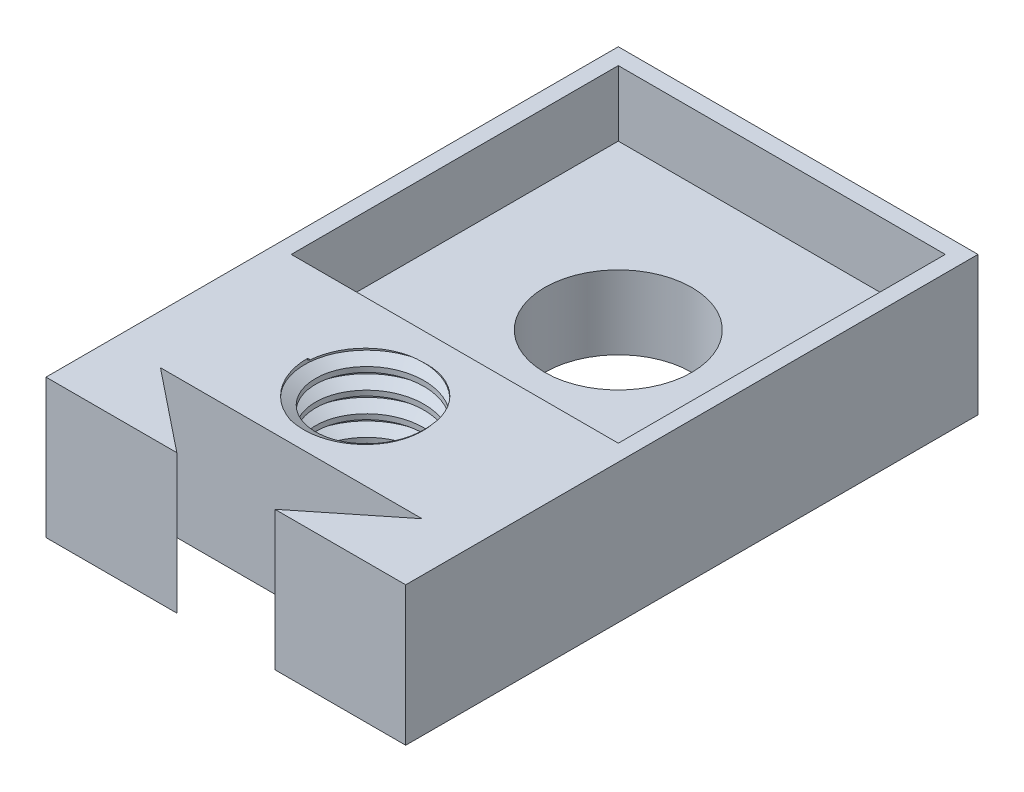
SolidWorks part; units mm, degrees
ref_plane "Front Plane" through (0, 0, 0) normal (0, 0, 1) x (1, 0, 0)
ref_plane "Top Plane" through (0, 0, 0) normal (0, 1, 0) x (1, 0, 0)
ref_plane "Right Plane" through (0, 0, 0) normal (1, 0, 0) x (0, 0, -1)
sketch "Sketch1" plane through (0, 0, 0) normal (0, 1, 0) x (1, 0, 0)
  line L1 (-10, -10) -> (10, -10)
  line L2 (-10, -10) -> (-10, 10)
  line L3 (-10, 10) -> (10, 10)
  line L4 (10, -10) -> (10, 10)
  line L5 (-10, -10) -> (10, 10) construction
  line L6 (-10, 10) -> (10, -10) construction
  line L7 (-11, -11) -> (11, -11)
  line L8 (-11, -11) -> (-11, 11)
  line L9 (-11, 11) -> (11, 11)
  line L10 (11, -11) -> (11, 11)
  line L11 (-11, -11) -> (11, 11) construction
  line L12 (-11, 11) -> (11, -11) construction
  point P0 (0, 0)
  point P6 (0, 0)
  dimension "D1" = 20
  dimension "D2" = 20
  dimension "D3" = 22
  dimension "D4" = 22
extrude "Boss-Extrude1" add sketch "Sketch1" along normal blind 5 and the other way blind 3.5
extrude "Boss-Extrude2" add sketch "Sketch1<2>" along normal blind 1 and the other way blind 3.5 contours L1 L4 L3 L2
sketch "Sketch1<2>" plane through (0, 0, 0) normal (0, 1, 0) x (1, 0, 0) same geometry as "Sketch1"
sketch "Sketch2" plane through (0, -3.5, 0) normal (0, -1, 0) x (1, 0, 0)
  circle A0 centre (0, 0) radius 4.5
  circle A1 centre (0, 0) radius 7
  dimension "D1" = 9
extrude "Cut-Extrude1" cut sketch "Sketch2" against normal blind 7 contours A0
sketch "Sketch3" plane through (0, 0, 0) normal (0, 1, 0) x (1, 0, 0)
  line L0 (0, -11) -> (0, -24)
  line L1 (-11, -11) -> (11, -11)
  line L2 (-11, -11) -> (-11, -24)
  line L3 (-11, -24) -> (11, -24)
  line L4 (11, -11) -> (11, -24)
  line L5 (-10.75, -24) -> (0, -24)
  line L6 (-8, -20) -> (-8, -24)
  line L7 (-10.75, -24) -> (-9.9027, -24)
  line L8 (-8, -20) -> (8, -20)
  line L9 (-8, -24) -> (8, -24)
  line L10 (-10.75, -24) -> (-13.75, -24)
  line L11 (0, -24) -> (-2.0006, -24)
  line L12 (0, -24) -> (-1, -24)
  line L13 (-11, 11) -> (-11, -11) construction
  line L14 (-1, -24) -> (-1, -21.75)
  line L15 (0, -24) -> (-3, -24)
  line L16 (10.75, -24) -> (13.75, -24)
  line L17 (8, -20) -> (8, -24)
  line L18 (-8, -20) -> (8, -24) construction
  line L19 (-8, -24) -> (8, -20) construction
  line L20 (-11, -9) -> (-11, -11)
  line L21 (11, -9) -> (11, -11)
  line L22 (10.75, -24) -> (0, -24)
  line L23 (-8, -20) -> (-3, -24)
  line L24 (1, -24) -> (1, -21.75)
  line L25 (8, -20) -> (3, -24)
  spline S0 degree 1 poles (-8, -20) (-1, -21.75) knots 0 0 1 1
  spline S1 degree 1 poles (8, -20) (1, -21.75) knots 0 0 1 1
  point P9 (0, -22)
  dimension "D1" = 10.75
  dimension "D3" = 13
  dimension "D4" = 3
  dimension "D5" = 4
  dimension "D9" = 0
extrude "Boss-Extrude4" add sketch "Sketch3" along normal blind 5 and the other way blind 3.5 contours L2 L20 L10 | L6 L8 L0 L1 L2 L3 L5 | L8 L17 L3 L4 L1 L0 | L23 L6 L5 | L17 L25 L3 region at (5.9324, 0, 16.2027) region at (-5.9324, 0, 16.2027) region at (-6.3333, 0, 22.6667) region at (6.3333, 0, 22.6667)
sketch "Sketch4" plane through (0, 5, 0) normal (0, 1, 0) x (1, 0, 0)
  line L2 (0, -4.675) -> (0, 4.675) construction
  line L4 (3, -24) -> (11, -24) construction
  circle A0 centre (0, -15) radius 4
  dimension "D2" = 8
  dimension "D1" = 9
extrude "Cut-Extrude2" cut sketch "Sketch4" against normal blind 10
thread "Thread1" pitch 1.25 method extrude trim with start face yes trim with end face yes profile "Thread Profile2" start angle 0, offset 1, length 10, pitch 1.25, diameter 8
ref_plane "Plane2" through (-4, 6, 15) normal (0, 0, 1) x (-1, 0, 0)
sketch "Thread Profile2" plane through (-4, 6, 15) normal (0, 0, 1) x (-1, 0, 0)
  line L0 (0, 0) -> (0, 1.25) construction
  line L11 (0, 0) -> (0, 1.0937)
  line L12 (0, 1.0937) -> (-0.6766, 0.7031)
  line L13 (-0.6766, 0.7031) -> (-0.6766, 0.3906)
  line L15 (-0.6766, 0.3906) -> (0, 0)
  line L17 (-0.6766, 0.5469) -> (0, 0.5469) construction
  point P2 (0, 0)
  dimension "Pitch" = 1.25
  dimension "Profile_Angle" = 60
  dimension "Profile_Land" = 0.3125
  dimension "Profile_Height" = 0.6766
